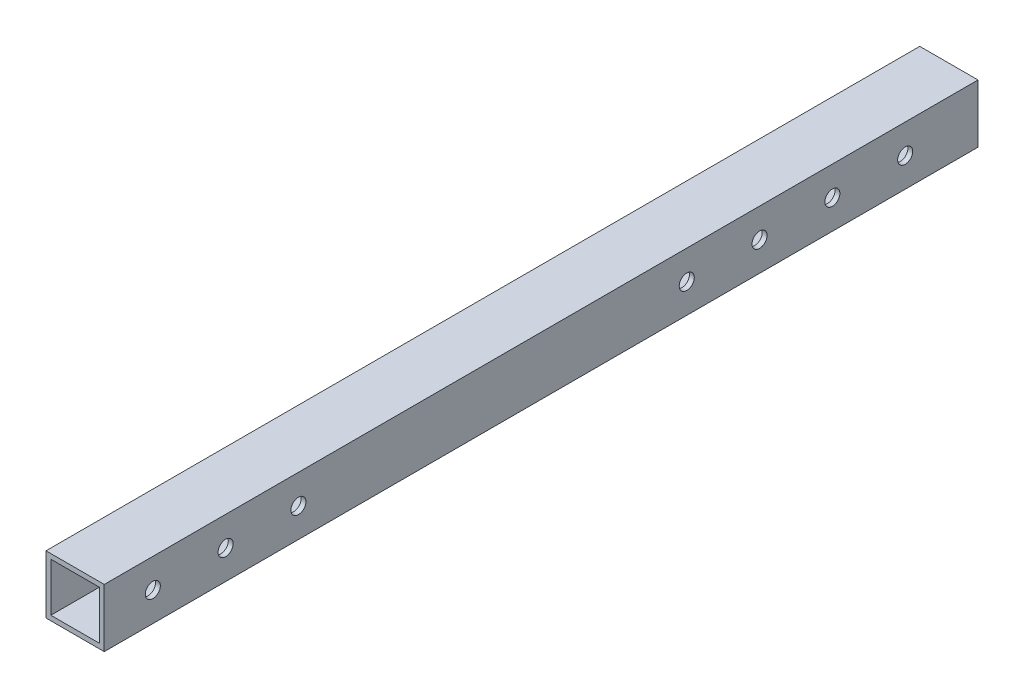
SolidWorks part; units mm, degrees
material "Thornel Mat VMA"
ref_plane "前视基准面" through (0, 0, 0) normal (0, 0, 1) x (1, 0, 0)
ref_plane "上视基准面" through (0, 0, 0) normal (0, 1, 0) x (1, 0, 0)
ref_plane "右视基准面" through (0, 0, 0) normal (1, 0, 0) x (0, 0, -1)
other "Configuration Table"
sketch "草图1" plane through (0, 0, 0) normal (0, 0, 1) x (1, 0, 0)
  line L0 (1, 1) -> (1, 11)
  line L1 (0, 0) -> (12, 0)
  line L2 (0, 0) -> (0, 12)
  line L3 (0, 12) -> (12, 12)
  line L4 (12, 0) -> (12, 12)
  line L5 (1, 11) -> (11, 11)
  line L6 (11, 1) -> (11, 11)
  line L7 (1, 1) -> (11, 1)
  dimension "D1" = 12
  dimension "D2" = 12
  dimension "D3" = 1
extrude "凸台-拉伸1" add sketch "草图1" along normal blind 180
sketch "草图3" plane through (12, 0, 0) normal (1, 0, 0) x (0, 1, 0)
  line L0 (6, 0) -> (6, 180) construction
  line L1 (0, 0) -> (12, 0) construction
  line L2 (0, 180) -> (12, 180) construction
  circle A0 centre (6, 30) radius 1.55
  circle A1 centre (6, 45) radius 1.55
  circle A2 centre (6, 60) radius 1.55
  circle A3 centre (6, 15) radius 1.55
  circle A4 centre (6, 170) radius 1.55
  circle A5 centre (6, 155) radius 1.55
  circle A6 centre (6, 140) radius 1.55
  dimension "D4" = 3.1
  dimension "D5" = 3.1
  dimension "D6" = 3.1
  dimension "D8" = 3.1
  dimension "D9" = 3.1
  dimension "D12" = 3.1
  dimension "D13" = 3.1
  dimension "D1" = 15
  dimension "D2" = 15
  dimension "D3" = 15
  dimension "D7" = 15
  dimension "D10" = 10
  dimension "D11" = 15
  dimension "D14" = 15
extrude "切除-拉伸1" cut sketch "草图3" against normal through all
